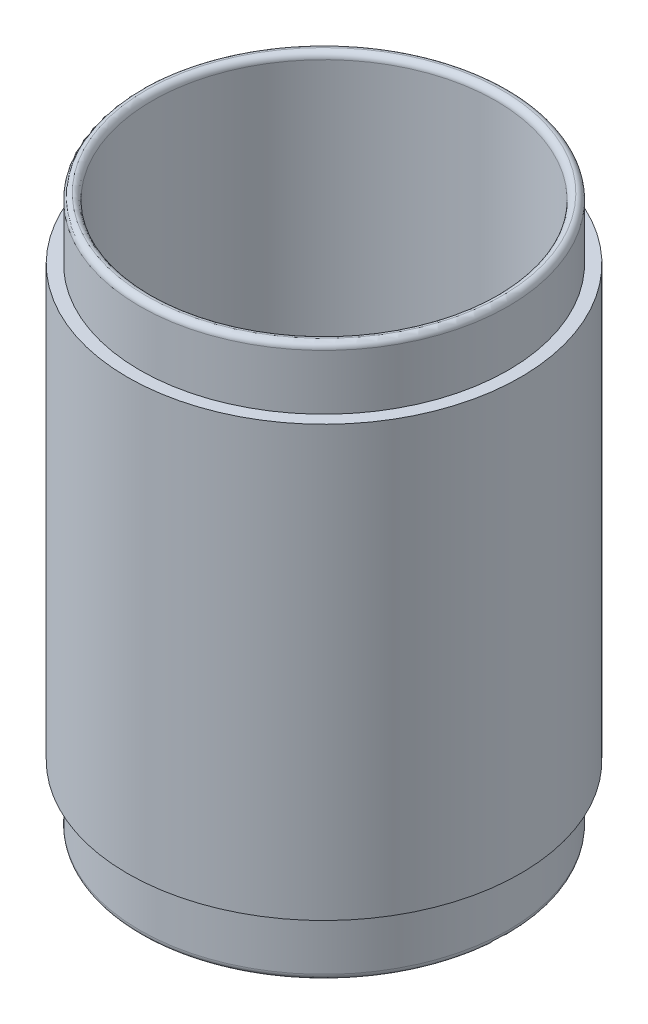
SolidWorks part; units mm, degrees
ref_plane "Front Plane" through (0, 0, 0) normal (0, 0, 1) x (1, 0, 0)
ref_plane "Top Plane" through (0, 0, 0) normal (0, 1, 0) x (1, 0, 0)
ref_plane "Right Plane" through (0, 0, 0) normal (1, 0, 0) x (0, 0, -1)
sketch "Sketch1" plane through (0, 0, 0) normal (0, 1, 0) x (1, 0, 0)
  circle A0 centre (0, 0) radius 16
  circle A1 centre (0, 0) radius 14
  dimension "D1" = 28
  dimension "D2" = 32
extrude "Boss-Extrude1" add sketch "Sketch1" along normal blind 35
sketch "Sketch2" plane through (0, 35, 0) normal (0, 1, 0) x (1, 0, 0)
  circle A0 centre (0, 0) radius 15
  circle A1 centre (0, 0) radius 14 construction
  circle A2 centre (0, 0) radius 14
  dimension "D1" = 30
extrude "Boss-Extrude2" add sketch "Sketch2" along normal blind 5
sketch "Sketch3" plane through (0, 0, 0) normal (0, -1, 0) x (1, 0, 0)
  circle A0 centre (0, 0) radius 15
  circle A1 centre (0, 0) radius 14 construction
  circle A2 centre (0, 0) radius 14
  dimension "D1" = 30
extrude "Boss-Extrude3" add sketch "Sketch3" along normal blind 5
fillet "Fillet1" radius 0.5 4 edges at (0, -5, -15) (0, 40, 15) (0, 40, 14) (0, -5, -14)
